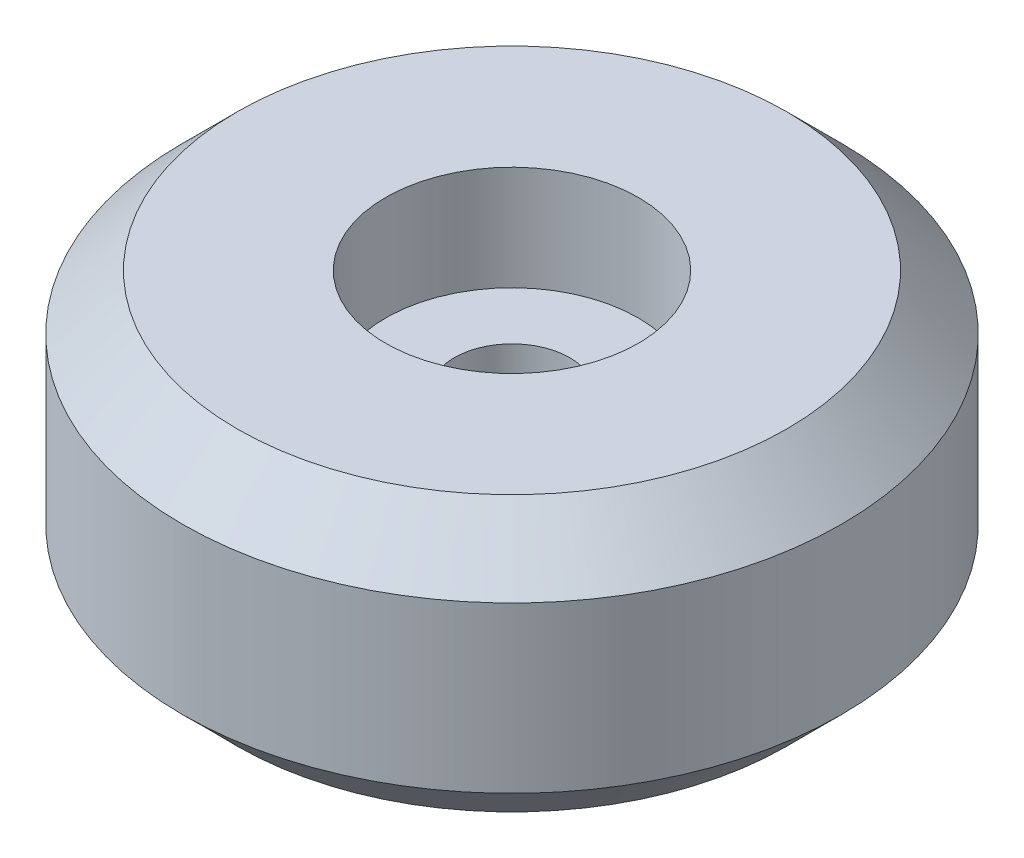
SolidWorks part; units mm, degrees
ref_plane "Front Plane" through (0, 0, 0) normal (0, 0, 1) x (1, 0, 0)
ref_plane "Top Plane" through (0, 0, 0) normal (0, 1, 0) x (1, 0, 0)
ref_plane "Right Plane" through (0, 0, 0) normal (1, 0, 0) x (0, 0, -1)
sketch "Sketch1" plane through (0, 0, 0) normal (0, 0, 1) x (1, 0, 0)
  line L0 (0, 0) -> (0, 8.4429) construction
  line L2 (4.6, 10.6822) -> (10, 10.6822)
  line L4 (10, 0.6822) -> (4.6, 0.6822)
  line L5 (12, 8.6822) -> (10, 10.6822)
  line L6 (12, 2.6822) -> (10, 0.6822)
  line L7 (12, 5.6822) -> (0, 5.6822) construction
  line L9 (12, 8.6822) -> (12, 2.6822)
  line L14 (4.6, 0.6822) -> (4.6, 4.4822)
  line L15 (4.6, 4.4822) -> (2.1, 4.4822)
  line L16 (2.1, 4.4822) -> (2.1, 6.8822)
  line L17 (2.1, 6.8822) -> (4.6, 6.8822)
  line L18 (4.6, 6.8822) -> (4.6, 10.6822)
  dimension "D1" = 3.8
  dimension "D2" = 4.6
  dimension "D3" = 10
  dimension "D4" = 6
  dimension "D5" = 2.1
  dimension "D6" = 3.8
  dimension "D7" = 12
  dimension "D8" = 4.6
revolve "Revolve1" add sketch "Sketch1" angle 360 about L0
